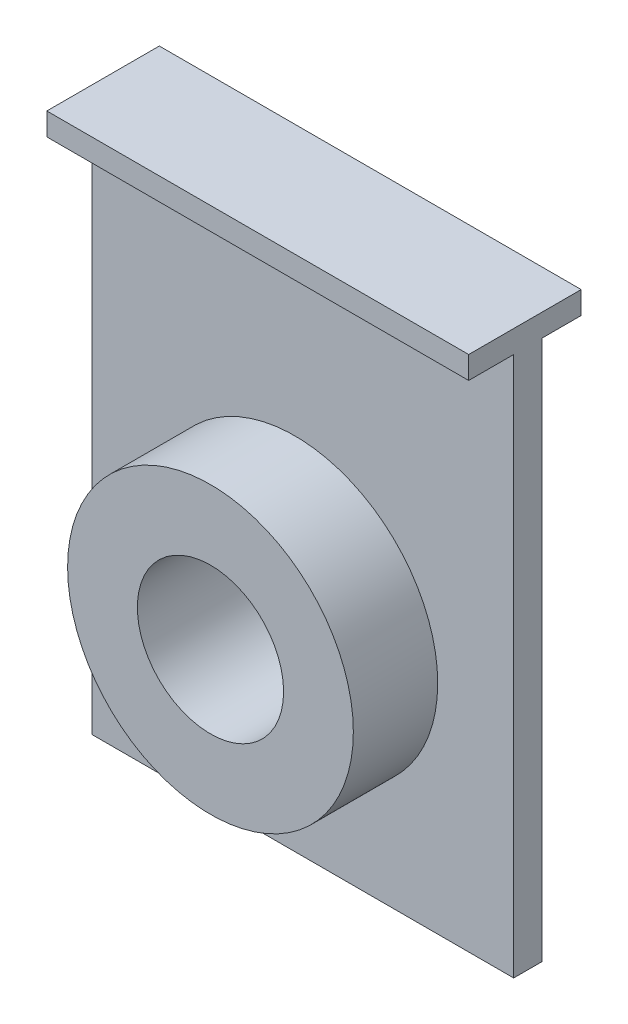
SolidWorks part; units mm, degrees
ref_plane "Front Plane" through (0, 0, 0) normal (0, 0, 1) x (1, 0, 0)
ref_plane "Top Plane" through (0, 0, 0) normal (0, 1, 0) x (1, 0, 0)
ref_plane "Right Plane" through (0, 0, 0) normal (1, 0, 0) x (0, 0, -1)
sketch "Sketch12" plane through (0, 0, 0) normal (0, 0, 1) x (1, 0, 0)
  line L0 (62.1258, 0) -> (62.1258, 100)
  line L1 (62.1258, 100) -> (137.1258, 100)
  line L2 (62.1258, 0) -> (137.1258, 0)
  line L3 (137.1258, 100) -> (137.1258, 0)
  circle A0 centre (99.6258, 37.5) radius 25.4
  circle A1 centre (99.6258, 37.5) radius 6.5
  dimension "D3" = 50.8
  dimension "D4" = 13
  dimension "D1" = 100
  dimension "D2" = 75
extrude "Boss-Extrude10" add sketch "Sketch12" along normal blind 5 separate body contours L1 L3 L2 L0
sketch "Sketch15" plane through (0, 0, 5) normal (0, 0, 1) x (1, 0, 0)
  circle A0 centre (98.2196, 38.6276) radius 25.4
  dimension "D1" = 50.8
extrude "Boss-Extrude11" add sketch "Sketch15" along normal blind 15
sketch "Sketch23" plane through (0, 0, 20) normal (0, 0, 1) x (1, 0, 0)
  circle A0 centre (98.2196, 38.6276) radius 13
  dimension "D1" = 26
extrude "Cut-Extrude7" cut sketch "Sketch23" against normal through all
sketch "Sketch24" plane through (0, 0, 5) normal (0, 0, 1) x (1, 0, 0)
  line L0 (62.1258, 100) -> (62.1258, 96)
  line L1 (62.1258, 0) -> (62.1258, 100) construction
  line L2 (62.1258, 96) -> (137.1258, 96)
  line L3 (137.1258, 100) -> (137.1258, 0) construction
  line L4 (137.1258, 96) -> (137.1258, 100)
  line L5 (137.1258, 100) -> (62.1258, 100)
  dimension "D1" = 4
extrude "Boss-Extrude13" add sketch "Sketch24" along normal blind 8 and the other way blind 12
